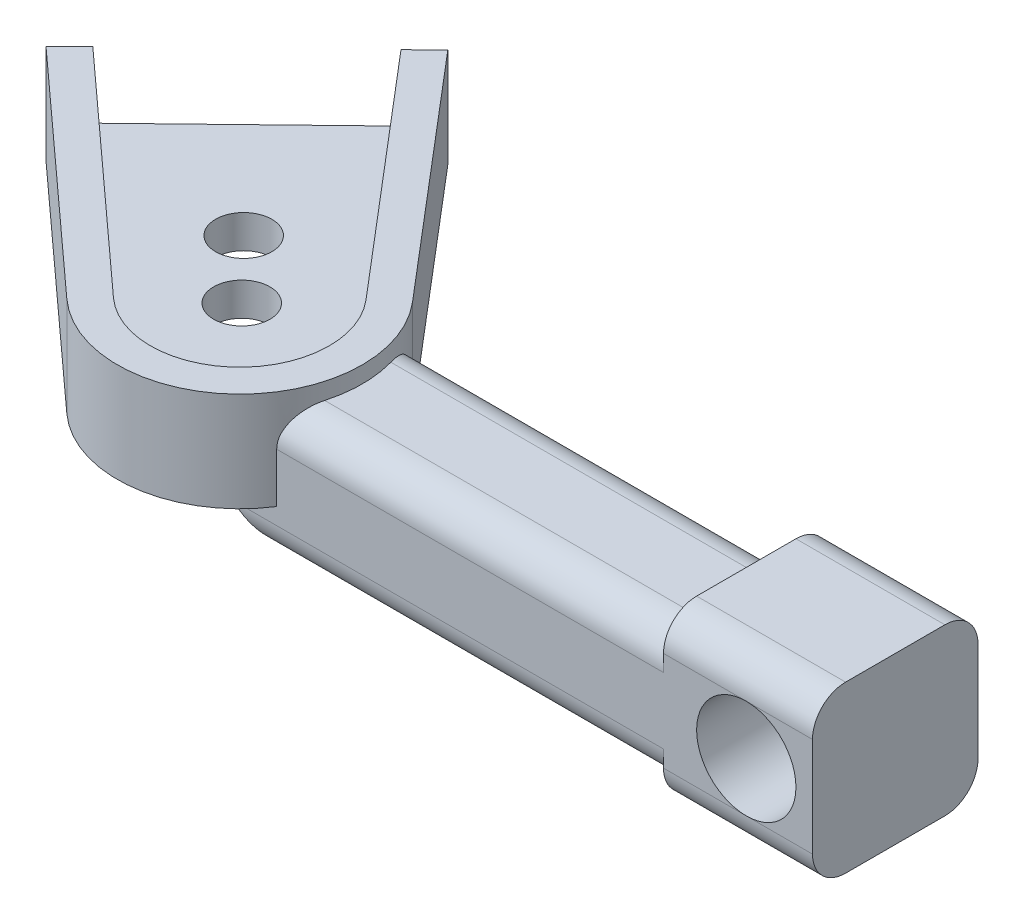
SolidWorks part; units mm, degrees
ref_plane "前视基准面" through (0, 0, 0) normal (0, 0, 1) x (1, 0, 0)
ref_plane "上视基准面" through (0, 0, 0) normal (0, 1, 0) x (1, 0, 0)
ref_plane "右视基准面" through (0, 0, 0) normal (1, 0, 0) x (0, 0, -1)
other "Configuration Table"
sketch "草图1" plane through (0, 0, 0) normal (0, 0, 1) x (1, 0, 0)
  line L1 (-10.25, 2) -> (10.25, 2)
  line L2 (-10.25, 2) -> (-10.25, -2)
  line L3 (-10.25, -2) -> (10.25, -2)
  line L4 (10.25, 2) -> (10.25, -2)
  line L5 (-10.25, 2) -> (10.25, -2) construction
  line L6 (-10.25, -2) -> (10.25, 2) construction
  point P0 (0, 0)
  dimension "D1" = 4
  dimension "D2" = 20.5
extrude "凸台-拉伸1" add sketch "草图1" along normal mid plane 4
sketch "草图2" plane through (0, -2, 0) normal (0, -1, 0) x (1, 0, 0)
  circle A0 centre (-9.0485, 0) radius 0.85
  dimension "D1" = 1.7
  dimension "D2" = 9.0485
extrude "切除-拉伸1" cut sketch "草图2" against normal blind 13
sketch "草图3" plane through (0, 0, 2) normal (0, 0, 1) x (1, 0, 0)
  line L0 (10.25, 0) -> (8.25, 0) construction
  line L1 (10.25, -2) -> (10.25, 2) construction
  circle A0 centre (8.25, 0) radius 0.8
  dimension "D2" = 1.6
  dimension "D1" = 2
extrude "切除-拉伸2" cut sketch "草图3" against normal blind 3
fillet "圆角1" radius 1 4 edges at (0, -2, -2) (0, 2, -2) (0, 2, 2) (0, -2, 2)
sketch "草图4" plane through (0, -2, 0) normal (0, -1, 0) x (1, 0, 0)
  line L4 (-10.25, 0.1366) -> (-6.25, 0.1366) construction
  line L5 (-10.25, 1) -> (-10.25, -1) construction
  line L6 (-6.25, -2) -> (-6.25, 2)
  line L7 (10.25, -2) -> (-10.25, -2) construction
  line L8 (-10.25, 2) -> (10.25, 2) construction
  line L9 (-6.25, 2) -> (-10.25, 2)
  line L10 (-10.25, 2) -> (-10.25, -2)
  line L11 (-10.25, -2) -> (-6.25, -2)
  point P1 (-7.4324, 0.1366)
  dimension "D1" = 4
  dimension "D2" = 7.4324
  dimension "D3" = 0.1366
extrude "切除-拉伸5" cut sketch "草图4" against normal blind 1.5
sketch "草图5" plane through (0, 2, 0) normal (0, 1, 0) x (1, 0, 0)
  line L0 (-10.25, 0) -> (-6.25, 0) construction
  line L1 (-10.25, -1) -> (-10.25, 1) construction
  line L2 (-6.25, 0) -> (-6.25, 2)
  line L3 (-6.25, 2) -> (-10.25, 2)
  line L4 (-10.25, 2) -> (-10.25, -2)
  line L5 (-10.25, -2) -> (-6.25, -2)
  line L6 (10.25, -2) -> (-10.25, -2) construction
  line L7 (-6.25, -2) -> (-6.25, 0)
  dimension "D1" = 4
  dimension "D2" = 2
extrude "切除-拉伸6" cut sketch "草图5" against normal blind 1.5
sketch "草图7" plane through (0, -0.5, 0) normal (0, -1, 0) x (1, 0, 0)
  line L0 (-10.25, 2) -> (-11.25, 2)
  line L1 (-11.25, 2) -> (-11.25, -2)
  line L2 (-11.25, -2) -> (-10.25, -2)
  line L3 (-10.25, 2) -> (-10.25, -2)
  dimension "D1" = 1
extrude "凸台-拉伸2" add sketch "草图7" against normal up to surface (1 mm away) up to face at (-8.25, 0.5, 0)
fillet "圆角2" radius 1 2 edges at (-11.25, 0, 2) (-11.25, 0, -2)
sketch "草图8" plane through (0, -0.5, 0) normal (0, -1, 0) x (1, 0, 0)
  line L3 (-13.011, -8.8308) -> (-6.9912, -1.7486)
  line L4 (-17.7429, -4.2527) -> (-10.8643, 1.9982)
  line L5 (-17.7429, -4.2527) -> (-18.4616, -3.5573)
  line L6 (-13.011, -8.8308) -> (-12.2924, -9.5262)
  line L7 (-12.2924, -9.5262) -> (-6.2298, -2.3969)
  line L8 (-18.4616, -3.5573) -> (-11.5374, 2.7377)
  arc A0 (-6.9912, -1.7486) -> (-10.8643, 1.9982) centre (-9.0485, 0) ccw
  arc A1 (-6.2298, -2.3969) -> (-11.5374, 2.7377) centre (-9.0485, 0) ccw
  dimension "D1" = 5.4
  dimension "D4" = 7.4
  dimension "D2" = 1
  dimension "D3" = 1
  dimension "D5" = 9.3579
  dimension "D6" = 9.2945
  dimension "D7" = 9.2949
  dimension "D8" = 7.1293
extrude "凸台-拉伸3" add sketch "草图8" against normal blind 3
sketch "草图9" plane through (0, -0.5, 0) normal (0, -1, 0) x (1, 0, 0)
  line L0 (-13.011, -8.8308) -> (-6.9894, -1.7514)
  line L1 (-13.011, -8.8308) -> (-17.7429, -4.2527)
  line L2 (-17.7429, -4.2527) -> (-10.8671, 1.9999)
  arc A0 (-6.9894, -1.7514) -> (-10.8671, 1.9999) centre (-9.0485, 0) ccw
  dimension "D1" = 2.7031
extrude "切除-拉伸7" cut sketch "草图9" against normal blind 3
extrude "凸台-拉伸4" add sketch "草图9<2>" against normal blind 1
sketch "草图9<2>" plane through (0, -0.5, 0) normal (0, -1, 0) x (1, 0, 0) same geometry as "草图9"
sketch "草图10" plane through (0, 0.5, 0) normal (0, 1, 0) x (1, 0, 0)
  circle A1 centre (-10.7868, 1.7967) radius 0.85
  circle A2 centre (-12.5252, 3.5934) radius 0.85
  dimension "D1" = 10.7868
  dimension "D5" = 1.7
  dimension "D6" = 1.7
  dimension "D2" = 1.7967
  dimension "D3" = 12.5252
  dimension "D4" = 3.5934
extrude "切除-拉伸8" cut sketch "草图10" against normal blind 1
sketch "草图11" plane through (0, 0, 2) normal (0, 0, 1) x (1, 0, 0)
  line L0 (-6.25, -2) -> (-6.25, -0.5)
  line L1 (-11.5374, -0.5) -> (-5.9356, -0.5) construction
  line L2 (-6.25, -0.5) -> (-6.25, -1) construction
  line L3 (-6.25, -0.5) -> (-7.75, -0.5)
  line L4 (-7.75, -0.5) -> (-6.25, -2)
  dimension "D1" = 1.5
extrude "凸台-拉伸5" add sketch "草图11" against normal up to surface (4 mm away) up to face at (-0.6452, -0.1667, -2)
sketch "草图12" plane through (-6.25, 0, 0) normal (1, 0, 0) x (0, 0, -1)
  line L0 (2, -1) -> (2, -2)
  line L1 (2, -2) -> (1, -2) construction
  line L2 (2, -2) -> (1, -2)
  line L3 (-1, -2) -> (-2, -2)
  line L4 (-2, -2) -> (-2, -1)
  arc A0 (1, -2) -> (2, -1) centre (1, -1) ccw
  arc A1 (-2, -1) -> (-1, -2) centre (-1, -1) ccw
extrude "切除-拉伸9" cut sketch "草图12" against normal through all
sketch "草图13" plane through (0, 0, 2) normal (0, 0, 1) x (1, 0, 0)
  line L0 (10.25, -2) -> (10.25, 2.5)
  line L1 (5.75, 2.5) -> (10.25, 2.5)
  line L2 (5.75, 2.5) -> (5.75, -2.5)
  line L3 (5.75, -2.5) -> (10.25, -2.5)
  line L5 (5.75, 2.5) -> (10.25, -2) construction
  line L6 (5.75, -2.5) -> (10.25, 2) construction
  line L7 (10.25, -2.5) -> (10.25, -2)
  point P0 (8.25, 0)
  dimension "D1" = 5
  dimension "D2" = 4.5
extrude "凸台-拉伸6" add sketch "草图13" against normal blind 5
sketch "草图14" plane through (0, 0, 2) normal (0, 0, 1) x (1, 0, 0)
  circle A0 centre (8.25, 0) radius 1.5
  dimension "D1" = 3
extrude "切除-拉伸10" cut sketch "草图14" against normal through all both and the other way through all
fillet "圆角3" radius 1 4 edges at (8, -2.5, -3) (8, 2.5, -3) (8, 2.5, 2) (8, -2.5, 2)
